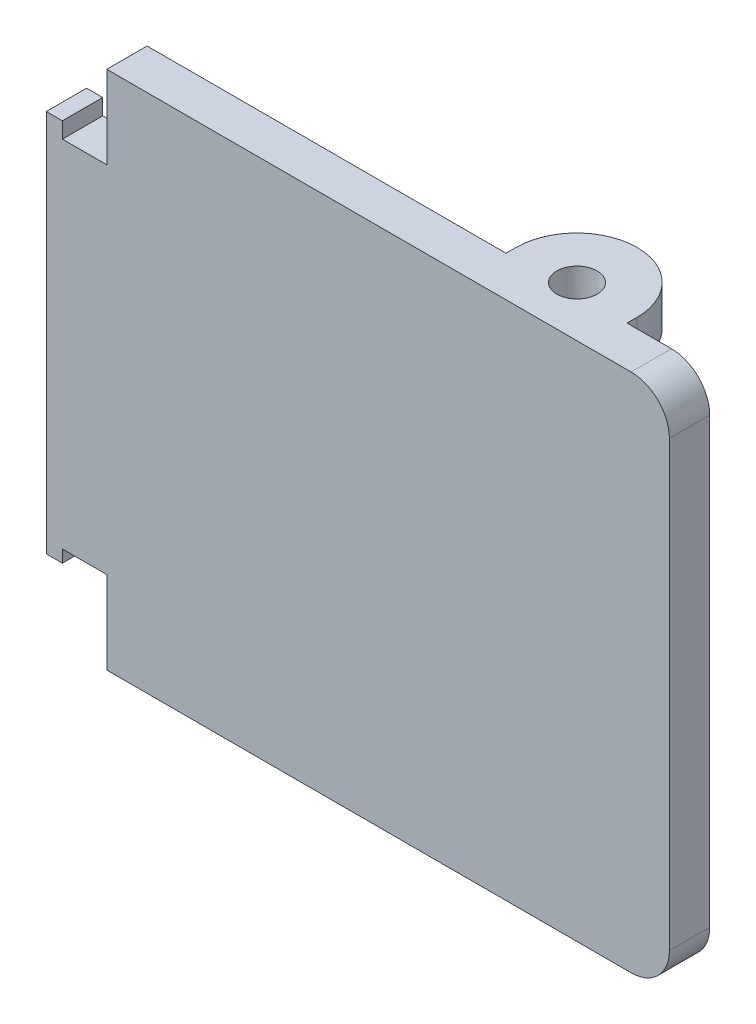
SolidWorks part; units mm, degrees
ref_plane "前视基准面" through (0, 0, 0) normal (0, 0, 1) x (1, 0, 0)
ref_plane "上视基准面" through (0, 0, 0) normal (0, 1, 0) x (1, 0, 0)
ref_plane "右视基准面" through (0, 0, 0) normal (1, 0, 0) x (0, 0, -1)
other "Configuration Table"
sketch "草图1" plane through (0, 0, 0) normal (0, 0, 1) x (1, 0, 0)
  line L0 (-14.1424, -0.7887) -> (-14.1424, 0)
  line L1 (-14.1424, 0) -> (-14.9424, 0)
  line L2 (-14.9424, 0) -> (-14.9424, -19)
  line L3 (-11.9424, 3.3113) -> (-11.9424, -0.7887)
  line L4 (-11.9424, 6.4113) -> (-11.9424, -25.5887) construction
  line L5 (-11.9424, -0.7887) -> (-14.1424, -0.7887)
  line L6 (-11.9424, -22.4887) -> (14.0576, -22.4887)
  line L7 (15.9576, -20.5887) -> (15.9576, 1.4113)
  line L8 (14.0576, 3.3113) -> (-11.9424, 3.3113)
  line L9 (-11.9424, -22.4887) -> (14.0576, -22.4887)
  line L10 (15.9576, -20.5887) -> (15.9576, 1.4113)
  line L11 (14.0576, 3.3113) -> (-11.9424, 3.3113)
  line L13 (-14.1424, -18.3887) -> (-11.9424, -18.3887)
  line L14 (-11.9424, -22.4887) -> (-11.9424, -18.3887)
  line L15 (-14.1424, -18.3887) -> (-14.1424, -19)
  line L16 (-14.1424, -19) -> (-14.9424, -19)
  arc A4 (14.0576, -22.4887) -> (15.9576, -20.5887) centre (14.0576, -20.5887) ccw
  arc A5 (15.9576, 1.4113) -> (14.0576, 3.3113) centre (14.0576, 1.4113) ccw
  arc A6 (14.0576, -22.4887) -> (15.9576, -20.5887) centre (14.0576, -20.5887) ccw
  arc A7 (15.9576, 1.4113) -> (14.0576, 3.3113) centre (14.0576, 1.4113) ccw
  point P6 (15.9576, -9.5887)
  point P11 (-14.9424, 0)
  point P14 (-15.2756, 0)
  point P15 (0, 0)
  point P17 (-14.1424, 0)
  point P19 (0, 0)
  point P25 (0, 0)
  point P26 (0, 0)
  point P27 (-14.0835, -19.1773)
  point P28 (-14.9424, 0)
  point P29 (-14.9424, 0)
  point P30 (0, 0)
  point P31 (0, 0)
  point P32 (0, 0)
  point P33 (0, 0)
  dimension "D2" = 17.6
  dimension "D3" = 2.2
  dimension "D4" = 0.8
  dimension "D5" = 19
  dimension "D1" = 0.1
extrude "凸台-拉伸1" add sketch "草图1" against normal blind 2
sketch "草图2" plane through (0, 0, -2) normal (0, 0, -1) x (-1, 0, 0)
  line L0 (11.9424, -22.4887) -> (-14.0576, -22.4887) construction
  line L1 (-5.8576, -22.4887) -> (-11.8576, -22.4887)
  line L2 (-5.8576, -22.4887) -> (-5.8576, -20.4887)
  line L3 (-5.8576, -20.4887) -> (-11.8576, -20.4887)
  line L4 (-11.8576, -22.4887) -> (-11.8576, -20.4887)
  line L5 (-14.0576, 3.3113) -> (11.9424, 3.3113) construction
  line L6 (-5.8576, 3.3113) -> (-11.8576, 3.3113)
  line L7 (-5.8576, 3.3113) -> (-5.8576, 1.3113)
  line L8 (-5.8576, 1.3113) -> (-11.8576, 1.3113)
  line L9 (-11.8576, 3.3113) -> (-11.8576, 1.3113)
  line L10 (-18.0576, -20.5887) -> (-18.0576, 1.4113) construction
  point P12 (0, 0)
  dimension "D1" = 6
  dimension "D2" = 6.2
  dimension "D3" = 2
extrude "凸台-拉伸2" add sketch "草图2" along normal blind 3.5
fillet "圆角1" radius 3 4 edges at (11.8576, 2.3113, -5.5) (5.8576, 2.3113, -5.5) (11.8576, -21.4887, -5.5) (5.8576, -21.4887, -5.5)
sketch "草图3" plane through (0, -22.4887, 0) normal (0, -1, 0) x (1, 0, 0)
  circle A0 centre (8.8741, -2.5) radius 1
  dimension "D1" = 2
extrude "切除-拉伸1" cut sketch "草图3" against normal blind 5 draft 2
sketch "草图4" plane through (0, 3.3113, 0) normal (0, 1, 0) x (1, 0, 0)
  circle A0 centre (8.8741, 2.5) radius 1
  dimension "D1" = 2
extrude "切除-拉伸2" cut sketch "草图4" against normal blind 5 draft 2
